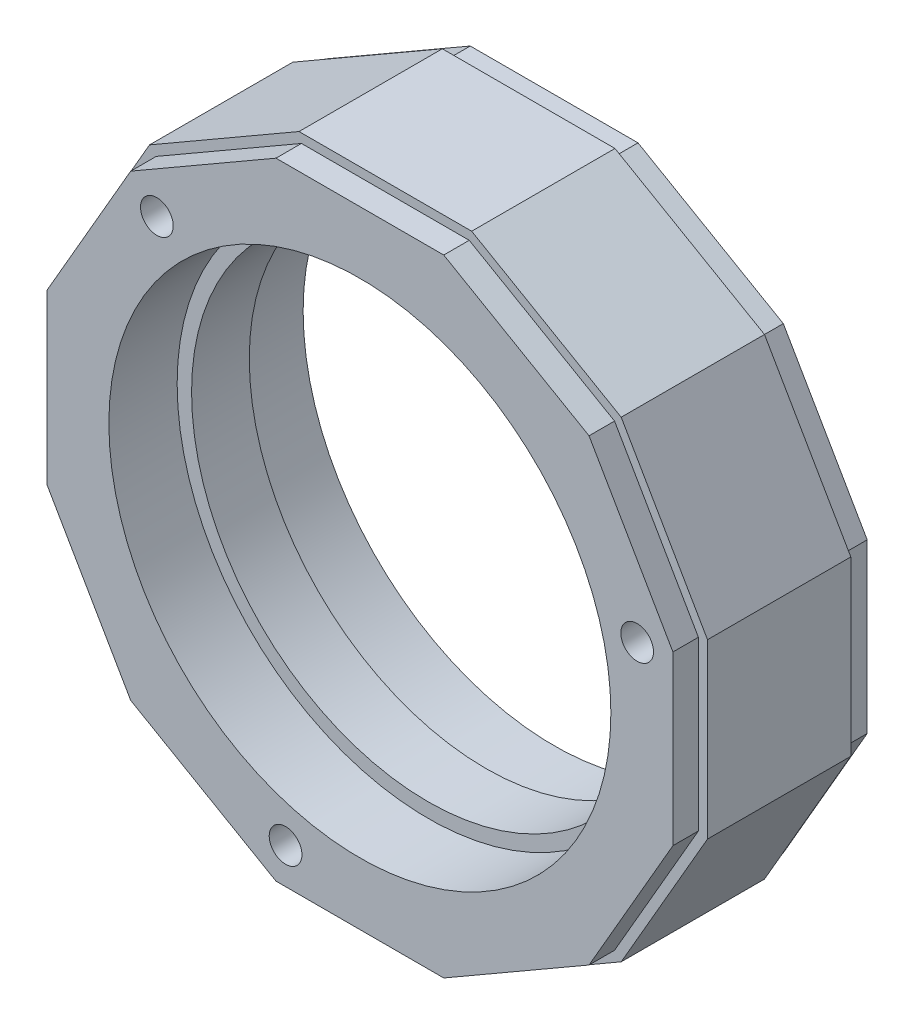
SolidWorks part; units mm, degrees
ref_plane "Front Plane" through (0, 0, 0) normal (0, 0, 1) x (1, 0, 0)
ref_plane "Top Plane" through (0, 0, 0) normal (0, 1, 0) x (1, 0, 0)
ref_plane "Right Plane" through (0, 0, 0) normal (1, 0, 0) x (0, 0, -1)
sketch "S01 - Smaller twelve-flat end bead seats" plane through (0, 0, 0) normal (0, 0, 1) x (1, 0, 0)
  line L0 (32.5517, 8.7222) -> (23.8295, 23.8295)
  line L1 (23.8295, 23.8295) -> (8.7222, 32.5517)
  line L2 (8.7222, 32.5517) -> (-8.7222, 32.5517)
  line L3 (-8.7222, 32.5517) -> (-23.8295, 23.8295)
  line L4 (-23.8295, 23.8295) -> (-32.5517, 8.7222)
  line L5 (-32.5517, 8.7222) -> (-32.5517, -8.7222)
  line L6 (-32.5517, -8.7222) -> (-23.8295, -23.8295)
  line L7 (-23.8295, -23.8295) -> (-8.7222, -32.5517)
  line L8 (-8.7222, -32.5517) -> (8.7222, -32.5517)
  line L9 (8.7222, -32.5517) -> (23.8295, -23.8295)
  line L10 (23.8295, -23.8295) -> (32.5517, -8.7222)
  line L11 (32.5517, -8.7222) -> (32.5517, 8.7222)
  circle A0 centre (0, 0) radius 24.6
  dimension "D1" = 49.2
  dimension "D2" = 8.7222
  dimension "D3" = 23.8295
  dimension "D4" = 32.5517
  dimension "D5" = 8.7222
  dimension "D6" = 23.8295
  dimension "D7" = 32.5517
  dimension "D8" = 8.7222
  dimension "D9" = 23.8295
  dimension "D10" = 32.5517
  dimension "D11" = 8.7222
  dimension "D12" = 23.8295
  dimension "D13" = 32.5517
extrude "01 - Smaller twelve-flat end bead seats" add sketch "S01 - Smaller twelve-flat end bead seats" along normal blind 20.2
sketch "S02 - Raised central tyre drive key" plane through (0, 0, 0) normal (0, 0, 1) x (1, 0, 0)
  line L0 (33.4983, 8.9758) -> (24.5225, 24.5225)
  line L1 (24.5225, 24.5225) -> (8.9758, 33.4983)
  line L2 (8.9758, 33.4983) -> (-8.9758, 33.4983)
  line L3 (-8.9758, 33.4983) -> (-24.5225, 24.5225)
  line L4 (-24.5225, 24.5225) -> (-33.4983, 8.9758)
  line L5 (-33.4983, 8.9758) -> (-33.4983, -8.9758)
  line L6 (-33.4983, -8.9758) -> (-24.5225, -24.5225)
  line L7 (-24.5225, -24.5225) -> (-8.9758, -33.4983)
  line L8 (-8.9758, -33.4983) -> (8.9758, -33.4983)
  line L9 (8.9758, -33.4983) -> (24.5225, -24.5225)
  line L10 (24.5225, -24.5225) -> (33.4983, -8.9758)
  line L11 (33.4983, -8.9758) -> (33.4983, 8.9758)
  circle A0 centre (0, 0) radius 24.6
  dimension "D1" = 49.2
  dimension "D2" = 8.9758
  dimension "D3" = 24.5225
  dimension "D4" = 33.4983
  dimension "D5" = 8.9758
  dimension "D6" = 24.5225
  dimension "D7" = 33.4983
  dimension "D8" = 8.9758
  dimension "D9" = 24.5225
  dimension "D10" = 33.4983
  dimension "D11" = 8.9758
  dimension "D12" = 24.5225
  dimension "D13" = 33.4983
extrude "02 - Raised central tyre drive key" add sketch "S02 - Raised central tyre drive key" along normal blind 14.9 from offset 2.65
sketch "S03 - Inboard 6808 outer race seat" plane through (0, 0, 0) normal (0, 0, 1) x (1, 0, 0)
  circle A0 centre (0, 0) radius 26.1
  dimension "D1" = 52.2
extrude "03 - Inboard 6808 outer race seat" cut sketch "S03 - Inboard 6808 outer race seat" along normal blind 7.2 from offset 0.1 offset against normal yes
sketch "S04 - Outboard 6808 outer race seat" plane through (0, 0, 0) normal (0, 0, 1) x (1, 0, 0)
  circle A0 centre (0, 0) radius 26.1
  dimension "D1" = 52.2
extrude "04 - Outboard 6808 outer race seat" cut sketch "S04 - Outboard 6808 outer race seat" along normal blind 7.2 from offset 13.1
sketch "S05 - Three tyre-flange through holes" plane through (0, 0, 0) normal (0, 0, 1) x (1, 0, 0)
  circle A0 centre (28.8329, 7.7257) radius 1.7
  circle A1 centre (-21.1071, 21.1071) radius 1.7
  circle A2 centre (-7.7257, -28.8329) radius 1.7
  dimension "D1" = 3.4
  dimension "D2" = 3.4
  dimension "D3" = 3.4
  dimension "D4" = 28.8329
  dimension "D5" = 7.7257
  dimension "D6" = 21.1071
  dimension "D7" = 7.7257
  dimension "D8" = 21.1071
  dimension "D9" = 28.8329
extrude "05 - Three tyre-flange through holes" cut sketch "S05 - Three tyre-flange through holes" along normal blind 20.4 from offset 0.1 offset against normal yes
